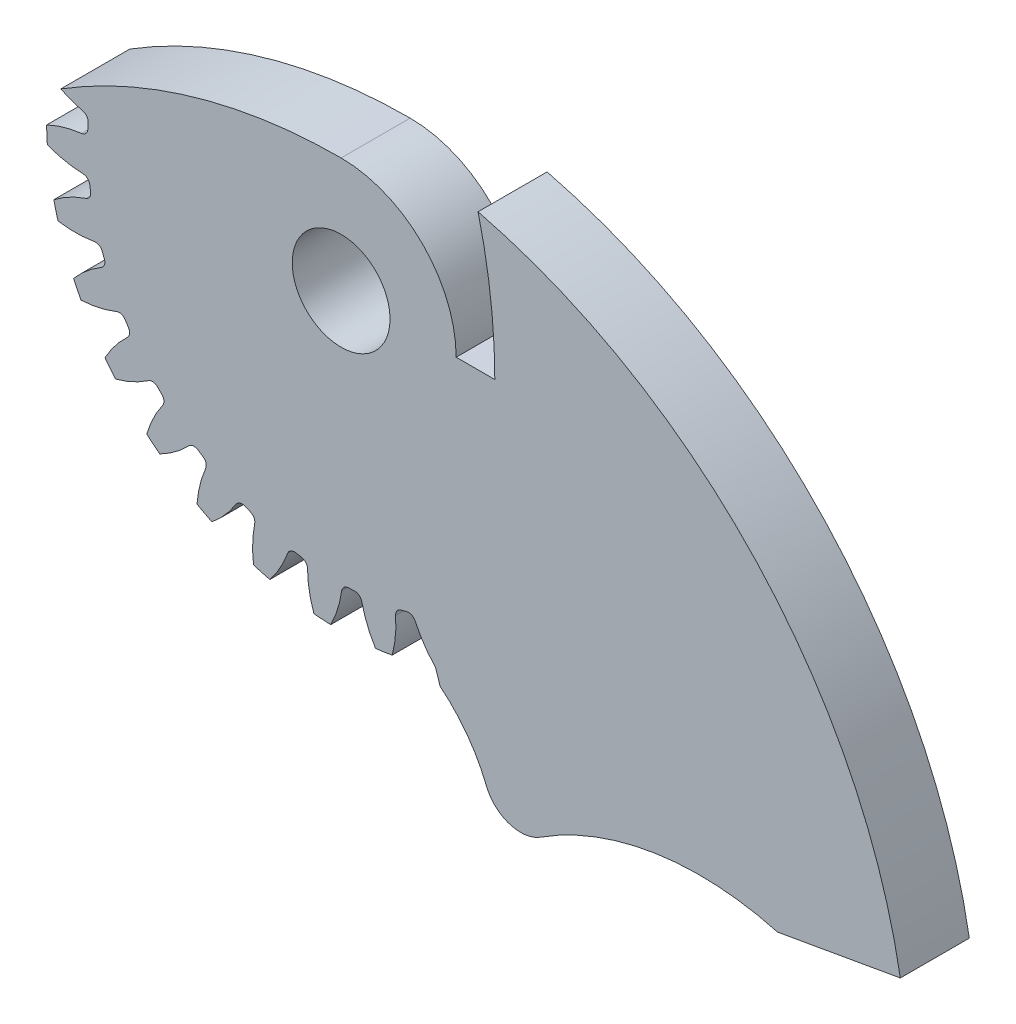
SolidWorks part; units mm, degrees
material "Delrin 2700 NC010, Low Viscosity Acetal Copolymer (SS)"
ref_plane "Front" through (0, 0, 0) normal (0, 0, 1) x (1, 0, 0)
ref_plane "Top" through (0, 0, 0) normal (0, 1, 0) x (1, 0, 0)
ref_plane "Right" through (0, 0, 0) normal (1, 0, 0) x (0, 0, -1)
sketch "Sketch3" plane through (0, 0, 0) normal (0, 0, 1) x (1, 0, 0)
  circle A0 centre (0, 0) radius 40.64
  dimension "od" = 81.28
extrude "gearBody" add sketch "Sketch3" along normal blind 9.525
sketch "Sketch2" plane through (0, 0, 0) normal (0, 0, 1) x (1, 0, 0)
  line L0 (0, 0) -> (34.0786, 14.1158) construction
  line L1 (45.4751, -11.4855) -> (0, 0) construction
  line L2 (0, 0) -> (36.3143, 0) construction
  line L3 (38.0972, -0.458) -> (37.8451, -4.4001) construction
  line L5 (37.9712, -2.4291) -> (0, 0) construction
  line L7 (0, 0) -> (36.8864, 0) construction
  arc A0 (36.879, -0.7403) -> (36.6727, -3.9649) centre (0, 0) ccw construction
  arc A1 (40.637, 0.4947) -> (40.2427, -5.6687) centre (0, 0) ccw construction
  arc A2 (38.0972, -0.458) -> (37.8451, -4.4001) centre (0, 0) ccw construction
  arc A3 (34.9015, -2.6404) -> (34.9534, -1.8283) centre (0, 0) ccw
  arc A4 (45.4751, -11.4855) -> (35.6466, -3.6712) centre (32.0022, -18.3431) ccw
  arc A5 (45.4751, -11.4855) -> (46.5679, 5.5974) centre (0, 0) ccw
  arc A6 (46.5679, 5.5974) -> (35.8238, -0.9008) centre (34.0786, 14.1158) cw
  arc A7 (34.9534, -1.8283) -> (35.8238, -0.9008) centre (35.9376, -1.8798) cw
  arc A8 (35.6466, -3.6712) -> (34.9015, -2.6404) centre (35.8842, -2.7147) cw
  point P6 (46.5679, 5.5974)
  point P22 (45.4751, -11.4855)
  dimension "baseDia" = 73.7729
  dimension "od" = 81.28
  dimension "pd" = 76.2
  dimension "rd" = 70.0024
  dimension "rFillet" = 0.9855
  dimension "pointX" = 46.5679
  dimension "pointY" = 5.5974
  dimension "CTT" = 3.9421
  dimension "flankCenterAngle" = 22.5
extrude "toothCut" cut sketch "Sketch2" along normal through all
pattern_circular "CirPattern1" count 30 over 360 about axis through (0, 0, 9.525) along (0, 0, -1) of "toothCut"
sketch "hub1Dia" plane through (0, 0, 0) normal (0, 0, -1) x (-1, 0, 0)
  circle A0 centre (0, 0) radius 12.7
  dimension "hub1Dia" = 25.4
sketch "hub2Dia" plane through (0, 0, 9.525) normal (0, 0, 1) x (1, 0, 0)
  circle A0 centre (0, 0) radius 12.7
  dimension "hub2dia" = 25.4
sketch "boreDia" plane through (0, 0, 0) normal (0, 0, 1) x (1, 0, 0)
  circle A0 centre (0, 0) radius 6.7469
  dimension "boreDia" = 13.4937
extrude "bore" cut sketch "boreDia" against normal mid plane 25400
sketch "Sketch4" plane through (0, 0, 9.525) normal (0, 0, 1) x (1, 0, 0)
  circle A0 centre (0, -57.15) radius 78.359
  arc A2 (-42.9159, 8.4119) -> (42.9159, 8.4119) centre (0, 0) cw
  dimension "D1" = 156.718
  dimension "D2" = 57.15
extrude "Cut-Extrude1" cut sketch "Sketch4" against normal through all contours A0 region at (0, 27.8712, 9.525)
sketch "Sketch5" plane through (0, 0, 9.525) normal (0, 0, 1) x (1, 0, 0)
  line L0 (0, 21.209) -> (21.5163, 7.6712)
  line L1 (21.5163, 7.6712) -> (8.9608, -26.928)
  line L2 (8.9608, -26.928) -> (13.028, -38.4952)
  line L3 (0, 0) -> (0, -57.15) construction
  line L4 (0, -57.15) -> (-49.4328, 3.6491) construction
  line L5 (0, -57.15) -> (67.8609, -96.3295) construction
  line L6 (13.6543, -40.4261) -> (13.028, -38.4952)
  line L9 (0, -57.15) -> (77.1686, -43.5431) construction
  line L12 (60.232, -46.5295) -> (77.1686, -43.5431)
  circle A1 centre (0, -57.15) radius 78.359 construction
  arc A5 (0, 21.209) -> (77.1686, -43.5431) centre (0, -57.15) cw
  circle A6 centre (0, -57.15) radius 21.59 construction
  arc A10 (20.0525, -49.1485) -> (13.6543, -40.4261) centre (0, -57.15) ccw
  circle A12 centre (49.4934, -85.725) radius 40.64 construction
  arc A13 (27.5177, -51.539) -> (60.232, -46.5295) centre (49.4934, -85.725) cw
  arc A14 (27.5177, -51.539) -> (20.0525, -49.1485) centre (24.7708, -47.2658) cw
  point P28 (21.569, -56.1981)
  dimension "D1" = 43.18
  dimension "D3" = 81.28
  dimension "D7" = 5.08
  dimension "D6" = 156.718
  dimension "D2" = 120
  dimension "D4" = 57.15
  dimension "D5" = 80
extrude "Boss-Extrude1" add sketch "Sketch5" against normal up to surface (9.525 mm away) up to face at (6.7469, 0, 0)
sketch "Sketch6" plane through (0, 0, 9.525) normal (0, 0, 1) x (1, 0, 0)
  line L1 (-41.2829, 3.086) -> (-43.5386, 8)
  line L2 (15.875, 0) -> (21.209, 0)
  circle A0 centre (0, -57.15) radius 78.359 construction
  arc A1 (77.1686, -43.5431) -> (-36.286, 12.3011) centre (0, -57.15) ccw construction
  circle A2 centre (0, 0) radius 15.875 construction
  arc A3 (0, 15.875) -> (15.875, 0) centre (0, 0) cw
  arc A4 (18.8964, 18.8964) -> (-43.5386, 8) centre (0, -57.15) ccw
  arc A5 (0, 15.875) -> (-41.2829, 3.086) centre (0, -57.15) ccw
  circle A6 centre (0, 0) radius 21.209 construction
  circle A8 centre (-57.15, 0) radius 78.359 construction
  arc A9 (21.209, 0) -> (18.8964, 18.8964) centre (-57.15, 0) ccw
  point P10 (-57.15, 0)
  dimension "D4" = 57.15
  dimension "D1" = 31.75
  dimension "D2" = 42.418
  dimension "D3" = 156.718
extrude "Cut-Extrude2" cut sketch "Sketch6" against normal through all
equation "\"Bodytube_OD\" = 6.17in"
equation "\"Bodytube_ID\" = 5.998in"
equation "\"Fwd_Tube_Length\" = 38in"
equation "\"Mid_Tube_Length\" = 8in"
equation "\"Aft_Section_Length\"= 40in"
equation "\"Mid_Coupler_Length\" = 13in"
equation "\"Aft_Lower_Length\"= 22in"
equation "\"AB_Coupler_OD_Length\"= 1in"
equation "\"AB_Coupling_Section_Length\"= 0.375in"
equation "\"AB_Coupler_Length\"= \"AB_Coupler_OD_Length\" + \"AB_Coupling_Section_Length\" * 2"
equation "\"Cutout_Angle\" = 80"
equation "\"AB_Paddle_Height\" = 0.375in"
equation "\"AB_Coupler_Num_Screws\"= 6"
equation "\"Num_Cutouts\" = 3"
equation "\"AB_Coupler_OD\"= 6.17in"
equation "\"AB_Coupler_ID\"= 5.75in"
equation "\"AB_Coupler_Surface_Diameter\"= 5.998in"
equation "\"AB_Coupling_Screw_Diameter\"= 0.1065in"
equation "\"AB_Central_Bushing_Length\" = .75in"
equation "\"Lead_Screw_Dist\" = 2.25in"
equation "\"Lead_Screw_Diam\" = (27/64)*1in"
equation "\"Lead_Screw_Length\" = (\"Mid_Coupler_Length\" + 2*0.375in + 2*0.5in)"
equation "\"Paddle_Pin_Offset\" = .25in"
equation "\"Paddle_Pin_Radius\" = 2.25in"
equation "\"Fwd_BKHD_From_Top\" = 18in"
equation "\"D1@Sketch4\"=\"Bodytube_OD\""
equation "\"D2@Sketch4\"=\"Paddle_Pin_Radius\""
equation "\"D3@Sketch5\"=\"Paddle_Gear_OD\""
equation "\"D4@Sketch5\"=\"Paddle_Pin_Radius\""
equation "\"Motor_OD\" = 4in"
equation "\"Aft_Upper_Length\"= \"Aft_Section_Length\" - \"Aft_Lower_Length\" - \"AB_Coupler_OD_Length\""
equation "\"Paddle_Gear_OD\" = 3.2in"
equation "\"D5@Sketch5\"=\"Cutout_Angle\""
equation "\"D6@Sketch5\"=\"Bodytube_OD\""
equation "\"D1@Sketch6\"=\"AB_Coupler_ID\"-2*\"Paddle_Pin_Radius\""
equation "\"D2@Sketch6\"=\"Bodytube_OD\"-2*\"Paddle_Pin_Radius\""
equation "\"D3@Sketch6\"=\"Bodytube_OD\""
equation "\"D4@Sketch6\"=\"Paddle_Pin_Radius\""
